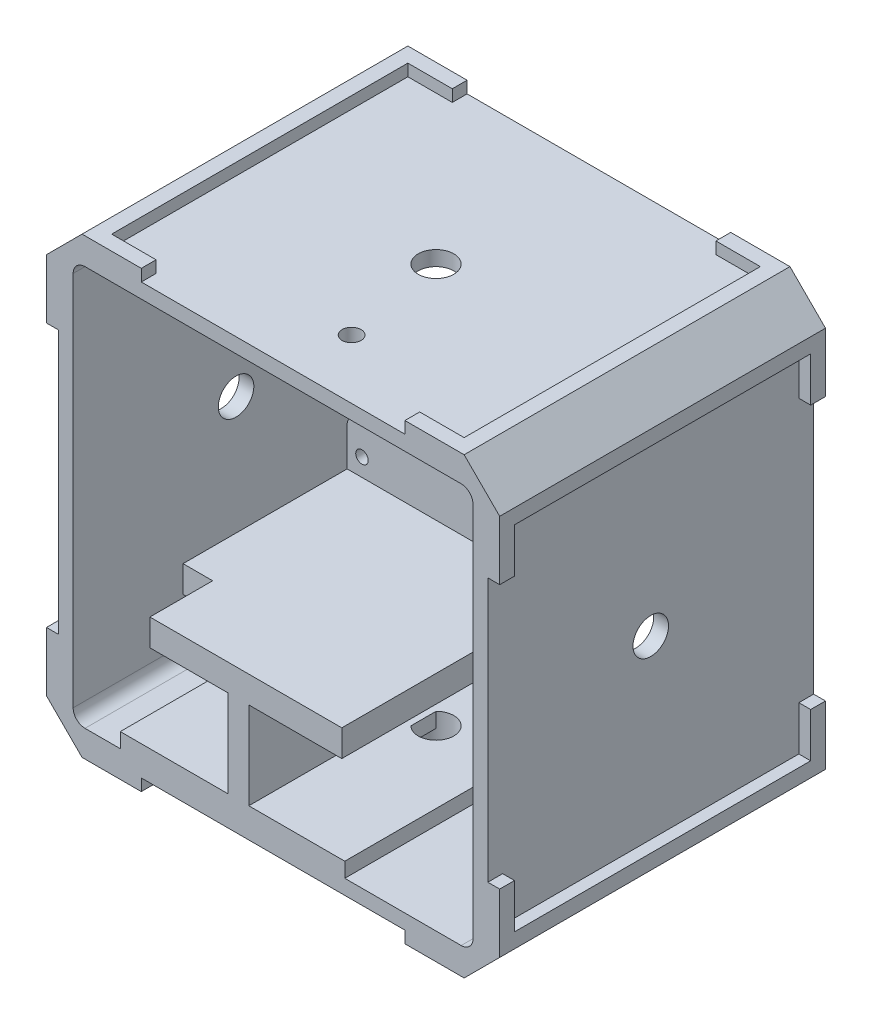
SolidWorks part; units mm, degrees
ref_plane "Front Plane" through (0, 0, 0) normal (0, 0, 1) x (1, 0, 0)
ref_plane "Top Plane" through (0, 0, 0) normal (0, 1, 0) x (1, 0, 0)
ref_plane "Right Plane" through (0, 0, 0) normal (1, 0, 0) x (0, 0, -1)
sketch "Sketch1" plane through (0, 0, 0) normal (0, 0, 1) x (1, 0, 0)
  line L0 (-33.75, -33.75) -> (33.75, -33.75) construction
  line L1 (-31.75, 33.75) -> (31.75, 33.75)
  line L2 (-33.75, 31.75) -> (-33.75, -31.75)
  line L3 (-31.75, -33.75) -> (31.75, -33.75)
  line L4 (33.75, 31.75) -> (33.75, -31.75)
  line L5 (-36.25, 32.25) -> (-36.25, -32.25)
  line L6 (33.75, 33.75) -> (33.75, -33.75) construction
  line L7 (-32.25, -36.25) -> (32.25, -36.25)
  line L8 (36.25, 32.25) -> (36.25, -32.25)
  line L9 (-32.25, 36.25) -> (32.25, 36.25)
  line L10 (-36.25, 36.25) -> (-36.25, -36.25) construction
  line L11 (-36.25, 36.25) -> (36.25, 36.25) construction
  line L12 (-33.75, 33.75) -> (33.75, 33.75) construction
  line L13 (-33.75, 33.75) -> (-33.75, -33.75) construction
  line L14 (-36.25, -36.25) -> (36.25, -36.25) construction
  line L15 (36.25, 36.25) -> (36.25, -36.25) construction
  line L16 (55, 0) -> (-55, 0) construction
  line L17 (0, -55) -> (0, 55) construction
  arc A0 (-36.25, 32.25) -> (-32.25, 36.25) centre (-32.25, 32.25) cw
  arc A1 (-31.75, 33.75) -> (-33.75, 31.75) centre (-31.75, 31.75) ccw
  arc A2 (-33.75, -31.75) -> (-31.75, -33.75) centre (-31.75, -31.75) ccw
  arc A3 (31.75, -33.75) -> (33.75, -31.75) centre (31.75, -31.75) ccw
  arc A4 (31.75, 33.75) -> (33.75, 31.75) centre (31.75, 31.75) cw
  arc A5 (-36.25, -32.25) -> (-32.25, -36.25) centre (-32.25, -32.25) ccw
  arc A6 (32.25, -36.25) -> (36.25, -32.25) centre (32.25, -32.25) ccw
  arc A7 (36.25, 32.25) -> (32.25, 36.25) centre (32.25, 32.25) ccw
  point P36 (-33.75, 0)
  point P39 (0, 33.75)
  dimension "D3" = 4
  dimension "D4" = 2
  dimension "D5" = 2
  dimension "D6" = 4
  dimension "D1" = 67.5
  dimension "D2" = 2.5
extrude "Boss-Extrude1" add sketch "Sketch1" along normal blind 55
sketch "Sketch2" plane through (0, 0, 0) normal (0, 0, 1) x (1, 0, 0)
  line L1 (-33.75, 33.75) -> (33.75, 33.75)
  line L2 (-33.75, 33.75) -> (-33.75, -33.75)
  line L3 (-33.75, -33.75) -> (33.75, -33.75)
  line L4 (33.75, 33.75) -> (33.75, -33.75)
extrude "Boss-Extrude2" add sketch "Sketch2" along normal blind 2.5
sketch "Sketch4" plane through (0, 0, 0) normal (0, 0, -1) x (-1, 0, 0)
  line L0 (-32.25, 36.25) -> (32.25, 36.25) construction
  line L1 (-36.25, -32.25) -> (-36.25, 32.25) construction
  circle A0 centre (-28.75, 28.75) radius 1.65
  dimension "D3" = 3.3
  dimension "D1" = 7.5
  dimension "D2" = 7.5
extrude "Cut-Extrude2" cut sketch "Sketch4" against normal up to next
mirror "Mirror1" about plane through (0, 0, 0) normal (1, 0, 0) of "Cut-Extrude2"
mirror "Mirror2" about plane through (0, 0, 0) normal (0, 1, 0) of "Mirror1"
sketch "Sketch5" plane through (0, 0, 0) normal (1, 0, 0) x (0, 0, -1)
  line L2 (-16.7, 12) -> (-16.7, -12)
  line L3 (-16.7, -12) -> (-62.4, -12)
  line L6 (-14.7, -14) -> (-64.4, -14)
  line L7 (-14.7, 12) -> (-14.7, -14)
  line L9 (-62.4, -12) -> (-64.4, -12)
  line L10 (-64.4, -12) -> (-64.4, -14)
  line L11 (-62.4, 12) -> (-62.4, -12) construction
  line L12 (-64.4, 14) -> (-64.4, -14) construction
  line L15 (-16.7, 12) -> (-14.7, 12)
  line L16 (-14.7, 14) -> (-14.7, -14) construction
  line L17 (-14.7, 14) -> (-64.4, 14) construction
  line L18 (-16.7, 12) -> (-62.4, 12) construction
  dimension "D1" = 24
  dimension "D2" = 49.7
  dimension "D3" = 2
extrude "Boss-Extrude3" add sketch "Sketch5" along normal blind 14.6 and the other way blind 25.8 separate body
sketch "Sketch6" plane through (0, 0, 64.4) normal (0, 0, 1) x (1, 0, 0)
  line L0 (-25.8, -14) -> (14.6, -14) construction
  line L1 (-25.8, -14) -> (12.1, -14)
  line L2 (-25.8, -14) -> (-25.8, -16.5)
  line L3 (-25.8, -16.5) -> (-7.6, -16.5)
  line L4 (12.1, -14) -> (12.1, -16.5)
  line L5 (-31.75, -33.75) -> (31.75, -33.75) construction
  line L6 (-25.8, -33.75) -> (12.1, -33.75)
  line L7 (-25.8, -33.75) -> (-25.8, -31.25)
  line L8 (-25.8, -31.25) -> (-7.6, -31.25)
  line L9 (12.1, -33.75) -> (12.1, -31.25)
  line L10 (-4.1, -16.5) -> (12.1, -16.5)
  line L12 (-7.6, -16.5) -> (-7.6, -31.25)
  line L14 (-4.1, -16.5) -> (-4.1, -31.25)
  line L15 (-4.1, -31.25) -> (12.1, -31.25)
  line L16 (-25.8, -12) -> (-25.8, -14) construction
  dimension "D1" = 2.5
  dimension "D2" = 2.5
  dimension "D3" = 37.9
  dimension "D4" = 37.9
  dimension "D5" = 3.5
  dimension "D6" = 18.2
  dimension "D7" = 18.2
extrude "Boss-Extrude4" add sketch "Sketch6" against normal blind 47
sketch "Sketch7" plane through (0, 0, 64.4) normal (0, 0, 1) x (1, 0, 0)
  line L0 (-25.8, -12) -> (-25.8, -16.5) construction
  line L1 (-25.8, -14.25) -> (12.1, -14.25)
  line L2 (-25.8, -14.25) -> (-25.8, -33.75)
  line L3 (-25.8, -33.75) -> (12.1, -33.75)
  line L4 (12.1, -14.25) -> (12.1, -33.75)
  line L5 (12.1, -33.75) -> (31.75, -33.75) construction
  line L6 (12.1, -33.75) -> (12.1, -31.25) construction
extrude "Cut-Extrude3" cut sketch "Sketch7" against normal blind 9.4
ref_plane "Plane1" through (-11.1, 0, 0) normal (-1, 0, 0) x (0, 0, 1)
sketch "Sketch10" [suppressed] plane through (-36.25, 0, 0) normal (-1, 0, 0) x (0, 0, 1)
  circle A0 centre (22.3967, 9) radius 1.5
  circle A1 centre (22.3967, -9) radius 1.5
  dimension "D1" = 3
  dimension "D2" = 3
extrude "Cut-Extrude4" [suppressed] cut sketch "Sketch10" against normal through all
sketch "Sketch12" plane through (0, 36.25, 0) normal (0, 1, 0) x (1, 0, 0)
  line L0 (-32.25, -55) -> (-32.25, 0) construction
  line L1 (32.25, -55) -> (29.75, -55)
  line L2 (32.25, -55) -> (32.25, -45)
  line L3 (32.25, -45) -> (29.75, -45)
  line L4 (29.75, -52.5) -> (29.75, -45)
  line L5 (32.25, -55) -> (22.25, -55)
  line L6 (32.25, -55) -> (32.25, -52.5)
  line L7 (29.75, -52.5) -> (22.25, -52.5)
  line L8 (22.25, -55) -> (22.25, -52.5)
  line L10 (-32.25, 0) -> (-32.25, -10)
  line L11 (-32.25, -10) -> (-29.75, -10)
  line L12 (-29.75, -2.5) -> (-29.75, -10)
  line L13 (-32.25, 0) -> (-22.25, 0)
  line L15 (-29.75, -2.5) -> (-22.25, -2.5)
  line L16 (-22.25, 0) -> (-22.25, -2.5)
  line M6 (-32.25, -55) -> (32.25, -55)
  line M7 (32.25, -55) -> (32.25, 0)
  dimension "D1" = 2.5
  dimension "D2" = 10
  dimension "D3" = 2.5
  dimension "D4" = 10
  dimension "D5" = 2.5
extrude "Boss-Extrude7" add sketch "Sketch12" along normal blind 2 contours L8 L2 L3 L4 L7 M6 M7 | L10 L11 L12 L15 L16 L13 region at (31, 36.25, 54.8586)
sketch "Sketch13" plane through (0, 0, 0) normal (0, 0, -1) x (-1, 0, 0)
  line L3 (-33.75, 21.25) -> (-25.25, 21.25)
  line L4 (-21.25, 33.75) -> (-21.25, 25.25)
  line L6 (0, 35.42) -> (0, -35.42) construction
  line L8 (21.25, 33.75) -> (21.25, 25.25)
  line L9 (33.75, 21.25) -> (25.25, 21.25)
  line L12 (35.42, 0) -> (-35.42, 0) construction
  line L17 (33.75, -21.25) -> (25.25, -21.25)
  line L18 (21.25, -33.75) -> (21.25, -25.25)
  line L19 (-21.25, -33.75) -> (-21.25, -25.25)
  line L20 (-33.75, -21.25) -> (-25.25, -21.25)
  line L27 (-33.75, 21.25) -> (-33.75, -21.25)
  line L29 (33.75, 21.25) -> (33.75, -21.25)
  line L34 (-21.25, 33.75) -> (21.25, 33.75)
  line L36 (-21.25, -33.75) -> (21.25, -33.75)
  arc A2 (-25.25, 21.25) -> (-21.25, 25.25) centre (-25.25, 25.25) ccw
  arc A4 (25.25, 21.25) -> (21.25, 25.25) centre (25.25, 25.25) cw
  arc A7 (25.25, -21.25) -> (21.25, -25.25) centre (25.25, -25.25) ccw
  arc A8 (-25.25, -21.25) -> (-21.25, -25.25) centre (-25.25, -25.25) cw
  dimension "D3" = 4
extrude "Cut-Extrude6" cut sketch "Sketch13" against normal up to next and the other way through all
sketch "Sketch15" plane through (0, 36.25, 0) normal (0, 1, 0) x (1, 0, 0)
  line L0 (22.25, -55) -> (-32.25, -55) construction
  line L1 (33.75, -55) -> (33.75, -2.5) construction
  circle A0 centre (3.25, -45) radius 1.6
  dimension "D1" = 3.2
  dimension "D2" = 10
  dimension "D3" = 30.5
extrude "Cut-Extrude8" cut sketch "Sketch15" against normal up to surface (2.5 mm away) and the other way through all up to face at (0, 33.75, 15)
sketch "Sketch16" plane through (-33.75, 0, 0) normal (1, 0, 0) x (0, 0, -1)
  line L0 (-55, 36.25) -> (-10, 36.25) construction
  line L2 (-16, 28.7) -> (-16, 30.35)
  line L7 (-16, 30.35) -> (-8.5, 30.35)
  line L9 (-16, 28.7) -> (-8.5, 28.7)
  line L10 (-8.5, 30.35) -> (-8.5, 28.7)
  line L12 (0, -32.25) -> (0, 32.25) construction
  dimension "D1" = 7.5
  dimension "D2" = 7.55
  dimension "D3" = 16
  dimension "D4" = 1.65
extrude "Boss-Extrude8" add sketch "Sketch16" along normal blind 7
sketch "Sketch17" plane through (0, 0, 14.7) normal (0, 0, -1) x (-1, 0, 0)
  line L0 (-14.6, -14) -> (-14.6, 12) construction
  line L2 (25.8, -14) -> (25.8, 12) construction
  line L3 (25.8, 12) -> (-14.6, 12) construction
  circle A0 centre (-12.1, 9) radius 1.05
  circle A1 centre (-12.1, -9) radius 1.05
  circle A2 centre (23.3, -9) radius 1.05
  dimension "D1" = 2.1
  dimension "D2" = 2.5
  dimension "D3" = 3
  dimension "D4" = 2.5
  dimension "D6" = 18
extrude "Cut-Extrude9" cut sketch "Sketch17" against normal up to next
sketch "Sketch19" plane through (0, 36.25, 0) normal (0, 1, 0) x (1, 0, 0)
  line L0 (32.25, -55) -> (-32.25, 0) construction
  line L1 (-32.25, 0) -> (-22.25, 0) construction
  line L2 (32.25, 0) -> (-32.25, -55) construction
  line L3 (32.25, -45) -> (32.25, 0) construction
  line L4 (32.25, 0) -> (-22.25, 0) construction
  line L5 (-32.25, 0) -> (-32.25, -10) construction
  line L6 (-32.25, 0) -> (-32.25, -10) construction
  circle A0 centre (0, -27.5) radius 3
  dimension "D1" = 6
extrude "Cut-Extrude10" cut sketch "Sketch19" against normal blind 2.5
sketch "Sketch20" plane through (36.25, 0, -36.25) normal (-1, 0, 0) x (0, 0, 1)
  line L0 (36.25, -32.25) -> (36.25, 32.25) construction
  line L1 (36.25, -32.25) -> (36.25, -22.25)
  line L2 (36.25, -32.25) -> (46.25, -32.25)
  line L3 (46.25, -32.25) -> (46.25, -29.75)
  line L4 (38.75, -29.75) -> (46.25, -29.75)
  line L5 (36.25, -32.25) -> (36.25, -22.25)
  line L7 (38.75, -29.75) -> (38.75, -22.25)
  line L8 (36.25, -22.25) -> (38.75, -22.25)
  line L10 (91.25, 32.25) -> (81.25, 32.25)
  line L11 (81.25, 32.25) -> (81.25, 29.75)
  line L12 (88.75, 29.75) -> (81.25, 29.75)
  line L13 (91.25, 32.25) -> (91.25, 22.25)
  line L15 (88.75, 29.75) -> (88.75, 22.25)
  line L16 (91.25, 22.25) -> (88.75, 22.25)
  line M25 (36.25, -32.25) -> (36.25, 32.25)
  line M26 (36.25, 32.25) -> (91.25, 32.25)
  line M27 (91.25, 32.25) -> (91.25, -32.25)
  line M28 (91.25, -32.25) -> (36.25, -32.25)
  dimension "D1" = 2.5
  dimension "D2" = 10
  dimension "D3" = 2.5
  dimension "D4" = 10
  dimension "D5" = 2.5
  dimension "D6" = 55
  dimension "D7" = 64.5
  dimension "D8" = 10
  dimension "D9" = 7.5
  dimension "D10" = 7.5
extrude "Boss-Extrude9" add sketch "Sketch20" against normal blind 2 contours L16 L15 L12 L11 M27 M26 | L8 L7 L4 L3 M25 M28 region at (36.25, -27.25, 0.1414) region at (36.25, 32.1086, 50)
ref_axis "Axis1" through (0, 0, 67.62) along (0, 0, -1)
pattern_circular "CirPattern1" count 4 every 90 about axis through (0, 0, 67.62) along (0, 0, -1) of "Boss-Extrude7", "Cut-Extrude10"
pattern_circular "CirPattern2" count 4 every 90 about axis through (0, 0, 67.62) along (0, 0, -1) of "Boss-Extrude9"
sketch "Sketch21" plane through (0, -33.75, 0) normal (0, -1, 0) x (1, 0, 0)
  line L0 (-2.11, 25.3674) -> (-2.11, 29.6326)
  arc A0 (-2.11, 25.3674) -> (-2.11, 29.6326) centre (0, 27.5) ccw
extrude "Cut-Extrude11" cut sketch "Sketch21" against normal blind 2.5
sketch "Sketch22" plane through (0, 0, 55) normal (0, 0, 1) x (1, 0, 0)
  line L0 (-38.25, 32.25) -> (-32.25, 38.25)
  line L1 (-32.25, 38.25) -> (-29.75, 38.25)
  line L8 (-29.75, 38.25) -> (-29.75, 33.75)
  line L13 (-38.25, 29.75) -> (-33.75, 29.75)
  line L20 (-38.25, 29.75) -> (-38.25, 32.25)
  line L24 (-32.25, 38.25) -> (-22.25, 38.25) construction
  line L26 (-33.75, 31.75) -> (-33.75, -31.75) construction
  line L27 (-38.25, 22.25) -> (-38.25, 32.25) construction
  line L28 (0, -35.42) -> (0, 35.42) construction
  line L29 (33.75, 33.75) -> (33.75, 29.75)
  line L30 (33.75, 33.75) -> (29.75, 33.75)
  line L31 (38.25, 29.75) -> (38.25, 32.25)
  line L32 (38.25, 29.75) -> (33.75, 29.75)
  line L33 (-33.75, 33.75) -> (-29.75, 33.75)
  line L34 (-33.75, 33.75) -> (-33.75, 29.75)
  line L37 (29.75, 38.25) -> (29.75, 33.75)
  line L38 (32.25, 38.25) -> (29.75, 38.25)
  line L39 (38.25, 32.25) -> (32.25, 38.25)
  line L40 (35.42, 0) -> (-35.42, 0) construction
  line L41 (38.25, -32.25) -> (32.25, -38.25)
  line L42 (32.25, -38.25) -> (29.75, -38.25)
  line L43 (29.75, -38.25) -> (29.75, -33.75)
  line L44 (-33.75, -33.75) -> (-33.75, -29.75)
  line L45 (-33.75, -33.75) -> (-29.75, -33.75)
  line L46 (38.25, -29.75) -> (33.75, -29.75)
  line L47 (38.25, -29.75) -> (38.25, -32.25)
  line L48 (33.75, -33.75) -> (29.75, -33.75)
  line L49 (33.75, -33.75) -> (33.75, -29.75)
  line L50 (-38.25, -29.75) -> (-38.25, -32.25)
  line L51 (-38.25, -29.75) -> (-33.75, -29.75)
  line L52 (-29.75, -38.25) -> (-29.75, -33.75)
  line L53 (-32.25, -38.25) -> (-29.75, -38.25)
  line L54 (-38.25, -32.25) -> (-32.25, -38.25)
  dimension "D1" = 2.5
  dimension "D2" = 2.5
extrude "Boss-Extrude12" add sketch "Sketch22" against normal through all
sketch "Sketch23" plane through (0, 0, 14.7) normal (0, 0, -1) x (-1, 0, 0)
  line L0 (25.8, 12) -> (-14.6, 12) construction
  line L1 (19.3, 12) -> (25.8, 12)
  line L2 (19.3, 12) -> (19.3, -4)
  line L3 (19.3, -4) -> (25.8, -4)
  line L4 (25.8, 12) -> (25.8, -4)
  line L5 (25.8, -14) -> (25.8, 12) construction
  circle A0 centre (23.3, -9) radius 1.05 construction
  dimension "D1" = 5
  dimension "D2" = 6.5
extrude "Cut-Extrude12" cut sketch "Sketch23" against normal up to next
sketch "Sketch24" plane through (14.6, 0, 0) normal (1, 0, 0) x (0, 0, -1)
  line L0 (-14.7, -14) -> (-14.7, 12) construction
  line L1 (-17.4, -16.5) -> (-17.4, -13.792)
  line L2 (-17.4, -13.792) -> (-14.7, -14)
  arc A0 (-14.7, -14) -> (-17.4, -16.5) centre (-17.4, -13.792) cw
extrude "Boss-Extrude13" add sketch "Sketch24" against normal up to surface (40.4 mm away) up to face at (-25.8, -12.15, 33.64)
fillet "Fillet2" radius 1.5 1 edges at (14.6, 12, 15.7)
chamfer "Chamfer1" distance 0.75 angle 45 3 edges at (-26.75, 30.35, 12.25) (-30.25, 30.35, 16) (-33.75, 28.7, 12.25)
sketch "Sketch25" plane through (0, -12, 0) normal (0, 1, 0) x (1, 0, 0)
  line L1 (14.6, -64.4) -> (11.6, -64.4)
  line L2 (14.6, -64.4) -> (14.6, -29.4)
  line L3 (14.6, -29.4) -> (11.6, -29.4)
  line L4 (11.6, -64.4) -> (11.6, -29.4)
  line L5 (-25.8, -64.4) -> (-20.8, -64.4)
  line L6 (-25.8, -64.4) -> (-25.8, -44.4)
  line L7 (-25.8, -44.4) -> (-20.8, -44.4)
  line L8 (-20.8, -64.4) -> (-20.8, -44.4)
  dimension "D1" = 3
  dimension "D2" = 35
  dimension "D3" = 5
  dimension "D4" = 20
extrude "Cut-Extrude13" cut sketch "Sketch25" against normal up to next
fillet "Fillet3" radius 1.5 3 edges at (-19.3, 12, 15.7) (-19.3, -4, 15.7) (-25.8, -4, 15.7)
sketch "Sketch26" plane through (11.6, 0, 0) normal (1, 0, 0) x (0, 0, -1)
  line L0 (-55, -22.25) -> (-55, 22.25) construction
  line L1 (-67.544, -8.4561) -> (-55, -8.4561)
  line L2 (-67.544, -8.4561) -> (-67.544, -18.0422)
  line L3 (-67.544, -18.0422) -> (-55, -18.0422)
  line L4 (-55, -8.4561) -> (-55, -18.0422)
extrude "Cut-Extrude14" cut sketch "Sketch26" against normal through all
